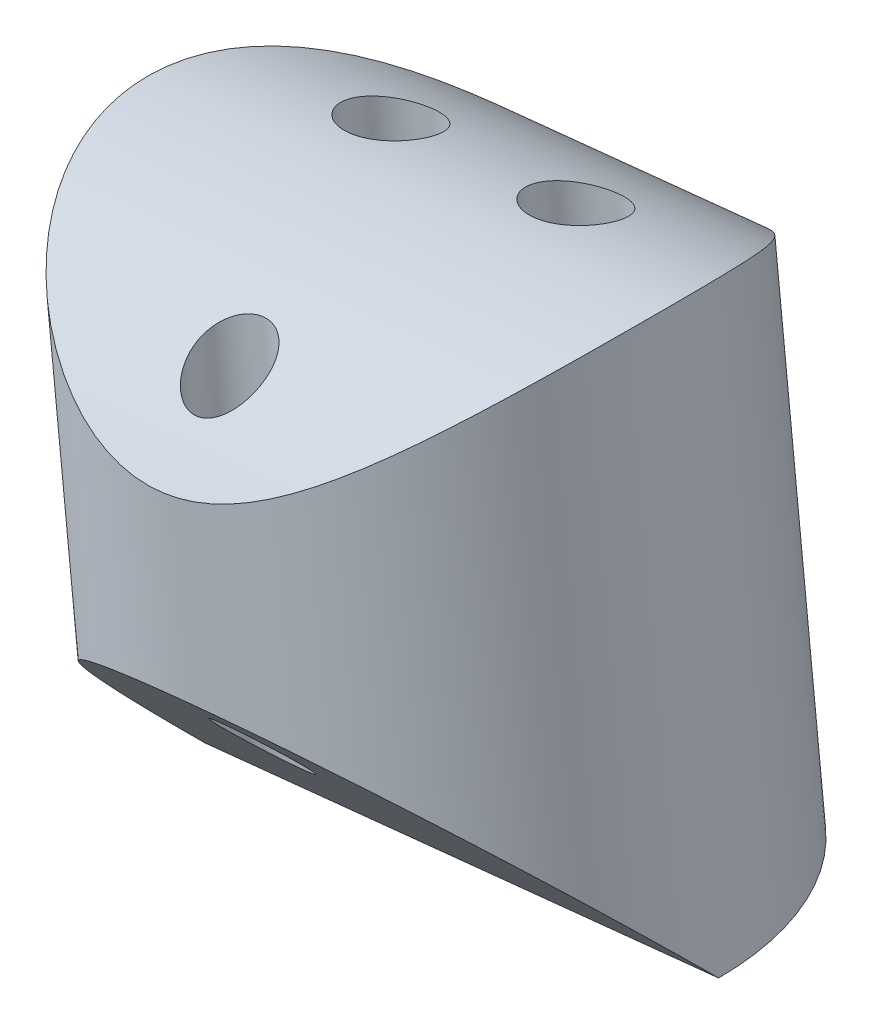
SolidWorks part; units mm, degrees
ref_plane "Front Plane" through (0, 0, 0) normal (0, 0, 1) x (1, 0, 0)
ref_plane "Top Plane" through (0, 0, 0) normal (0, 1, 0) x (1, 0, 0)
ref_plane "Right Plane" through (0, 0, 0) normal (1, 0, 0) x (0, 0, -1)
sketch "Sketch2" plane through (0, 0, 0) normal (0, 0, 1) x (1, 0, 0)
  line L0 (0, 0) -> (90, 0)
  line L1 (90, 0) -> (90, 120)
  line L2 (90, 120) -> (0, 120)
  line L3 (0, 120) -> (0, 0)
  line L4 (0, 120) -> (-10, 120)
  line L5 (-10, 120) -> (-10, 16.9491)
  line L6 (-10, 120) -> (57.5, 127)
  line L7 (57.5, 127) -> (90, 124)
  line L8 (90, 120) -> (99, 60)
  line L10 (90, 124) -> (90, 120)
  line L11 (5.9147, 0) -> (5.9147, -25)
  line L12 (5.9147, -25) -> (-4.0853, -25)
  line L13 (-4.0853, -29) -> (-4.0853, 0)
  line L14 (80, 0) -> (80, -25)
  line L15 (80, -25) -> (90, -25)
  line L16 (90, -29) -> (90, 0)
  line L17 (15.7927, 122.6748) -> (5.4776, 222.1414)
  line L18 (5.4776, 222.1414) -> (21.3923, 223.7918)
  line L19 (21.3923, 223.7918) -> (31.7073, 124.3252)
  line L20 (7.6492, 201.201) -> (23.5639, 202.8514)
  line L21 (10.9066, 169.7905) -> (26.8212, 171.441)
  line L22 (-10, 120) -> (-20.0396, 216.8108)
  line L23 (-20.0396, 216.8108) -> (-4.125, 218.4612)
  line L24 (-4.125, 218.4612) -> (5.9147, 121.6504)
  line L25 (-17.926, 196.4296) -> (-2.0114, 198.08)
  line L26 (-14.7556, 165.8578) -> (1.159, 167.5082)
  line L27 (57.5, 127) -> (46.9095, 229.1223)
  line L28 (46.9095, 229.1223) -> (30.9949, 227.4719)
  line L29 (30.9949, 227.4719) -> (41.5853, 125.3496)
  line L30 (33.2245, 205.9725) -> (49.1391, 207.6229)
  line L31 (36.5688, 173.7233) -> (52.4835, 175.3737)
  line L34 (90, 124) -> (99.1917, 223.5767)
  line L35 (99.1917, 223.5767) -> (83.2594, 225.0473)
  line L36 (83.2594, 225.0473) -> (74.0677, 125.4707)
  line L38 (81.3243, 204.0838) -> (97.2566, 202.6132)
  line L39 (78.4217, 172.6386) -> (94.354, 171.1679)
  line L40 (62.4078, 79.6749) -> (57.5, 127) construction
  line L41 (41.5853, 125.3496) -> (46.4931, 78.0244) construction
  line L42 (46.4931, 78.0244) -> (62.4078, 79.6749) construction
  line L43 (31.7073, 124.3252) -> (36.6151, 77.0001) construction
  line L44 (36.6151, 77.0001) -> (20.7005, 75.3496) construction
  line L45 (20.7005, 75.3496) -> (15.7927, 122.6748) construction
  line L46 (5.9147, 121.6504) -> (10.8224, 74.3253) construction
  line L47 (10.8224, 74.3253) -> (-5.0922, 72.6749) construction
  line L48 (-5.0922, 72.6749) -> (-10, 120) construction
  line L49 (74.0677, 125.4707) -> (69.6944, 78.0931) construction
  line L50 (69.6944, 78.0931) -> (85.7624, 78.0931) construction
  line L51 (85.7624, 78.0931) -> (90, 124) construction
  line L52 (-12.0823, 217.636) -> (10.4873, 0) construction
  line L53 (13.4349, 222.9666) -> (36.5574, 0) construction
  line L54 (38.9522, 228.2971) -> (62.6275, 0) construction
  line L55 (91.2256, 224.312) -> (70.5198, 0) construction
  line L59 (99, 60) -> (93.5277, 44.9649)
  line L60 (99, 60) -> (169.4769, 34.3485)
  line L61 (169.4769, 34.3485) -> (164.0046, 19.3134)
  line L62 (164.0046, 19.3134) -> (93.5277, 44.9649)
  line L63 (90, -2) -> (100, -2)
  line L64 (141.2862, 44.6091) -> (135.8138, 29.574)
  line L65 (99, 60) -> (55.7741, 75.7329) construction
  line L66 (55.7741, 75.7329) -> (50.3018, 60.6978) construction
  line L67 (100, -2) -> (100, -29)
  line L70 (-4.0853, -2) -> (-14.0853, -2)
  line L71 (-14.0853, -2) -> (-14.0853, -29)
  line L74 (-4.0853, 0) -> (0, 0)
  line L75 (-14.0853, -29) -> (-14.0853, -112.587)
  line L76 (-14.0853, -112.587) -> (100, -112.587)
  line L77 (100, -112.587) -> (100, -29)
  line L78 (-14.0853, -29) -> (100, -29)
  line L79 (-14.0853, -14.5) -> (100, -14.5) construction
  line L80 (31.7073, -112.587) -> (31.7073, -122.6232)
  line L81 (31.7073, -122.6232) -> (42.9573, -122.6232)
  line L82 (42.9573, -122.6232) -> (42.9573, -112.587)
  line L83 (-14.0853, -112.587) -> (-88.3667, -112.587)
  line L84 (-88.3667, -112.587) -> (-88.3667, -128.2699)
  line L85 (-88.3667, -128.2699) -> (169.4958, -128.2699)
  line L86 (169.4958, -128.2699) -> (169.4958, -112.587)
  line L87 (169.4958, -112.587) -> (100, -112.587)
  line L88 (90, 60) -> (-10, 60) construction
  line L89 (50.3018, 60.6978) -> (93.5277, 44.9649) construction
  line L90 (87.2806, 55.7521) -> (166.7408, 26.8309) construction
  line L91 (87.2806, 55.7521) -> (82.1749, 52.5336) construction
  line L92 (82.1749, 52.5336) -> (77.3257, 0) construction
  line L93 (83.1185, 56.6957) -> (86.337, 51.59) construction
  arc A0 (-10, 16.9491) -> (-4.0853, 0) centre (14.9876, 16.1624) ccw
  arc A1 (93.5277, 44.9649) -> (90, 0) centre (-126.4069, 39.5988) cw
  point P42 (41.1818, 206.7977)
  point P100 (84.7278, 54.1428)
  point P101 (84.7278, 54.1428)
  dimension "D11" = 47.3684
  dimension "D35" = 9
  dimension "D32" = 220
  dimension "D36" = 25
  dimension "D1" = 120
  dimension "D2" = 90
  dimension "D3" = 10
  dimension "D5" = 67.862
  dimension "D6" = 7
  dimension "D7" = 4
  dimension "D8" = 16
  dimension "D9" = 16
  dimension "D10" = 100
  dimension "D12" = 31.5789
  dimension "D13" = 16
  dimension "D14" = 16
  dimension "D15" = 16
  dimension "D16" = 25.7927
  dimension "D17" = 100
  dimension "D18" = 21.0526
  dimension "D19" = 31.5789
  dimension "D20" = 97.33
  dimension "D21" = 102.67
  dimension "D22" = 20.4905
  dimension "D23" = 30.7358
  dimension "D24" = 21.6147
  dimension "D25" = 32.4221
  dimension "D26" = 25
  dimension "D28" = 25
  dimension "D29" = 75
  dimension "D30" = 47.5789
  dimension "D31" = 30
  dimension "D33" = 46
  dimension "D34" = 20
  dimension "D37" = 2
  dimension "D38" = 2
  dimension "D39" = 27
  dimension "D40" = 10
  dimension "D41" = 10
  dimension "D42" = 27
  dimension "D43" = 14.5
  dimension "D44" = 127.5
ref_plane "Plane1" through (87.2806, 55.7521, 0) normal (-0.846, -0.5333, 0) x (0, 0, 1)
ref_plane "Plane2" through (82.1749, 52.5336, 0) normal (-0.0919, -0.9958, 0) x (-0.9958, 0.0919, 0)
ref_plane "Plane3" through (91.2256, 224.312, 0) normal (-0.0919, -0.9958, 0) x (-0.9958, 0.0919, 0)
ref_plane "Plane4" through (38.9522, 228.2971, 0) normal (0.1032, -0.9947, 0) x (-0.9947, -0.1032, 0)
ref_plane "Plane5" through (13.4349, 222.9666, 0) normal (0.1032, -0.9947, 0) x (-0.9947, -0.1032, 0)
ref_plane "Plane7" through (166.7408, 26.8309, 0) normal (0.9397, -0.342, 0) x (0, 0, -1)
ref_plane "Plane8" through (110.4217, -40.1902, 0) normal (0.9397, -0.342, 0) x (0, 0, -1)
ref_plane "Plane9" through (19.3664, 209.803, 0) normal (-0.0919, -0.9958, 0) x (-0.9958, 0.0919, 0)
ref_plane "Plane10" through (16.4638, 178.3578, 0) normal (-0.0919, -0.9958, 0) x (-0.9958, 0.0919, 0)
ref_plane "Plane11" through (-20.7793, 200.3721, 0) normal (0.1032, -0.9947, 0) x (-0.9947, -0.1032, 0)
ref_plane "Plane12" through (-17.435, 168.1229, 0) normal (0.1032, -0.9947, 0) x (-0.9947, -0.1032, 0)
ref_plane "Plane13" through (-20.5619, 198.2754, 0) normal (0.1032, -0.9947, 0) x (-0.9947, -0.1032, 0)
ref_plane "Plane14" through (-17.3045, 166.8649, 0) normal (0.1032, -0.9947, 0) x (-0.9947, -0.1032, 0)
ref_plane "Plane15" through (-12.0823, 217.636, 0) normal (0.1032, -0.9947, 0) x (-0.9947, -0.1032, 0)
ref_plane "Plane16" through (-20.3445, 196.1788, 0) normal (0.1032, -0.9947, 0) x (-0.9947, -0.1032, 0)
ref_plane "Plane17" through (-17.1741, 165.607, 0) normal (0.1032, -0.9947, 0) x (-0.9947, -0.1032, 0)
ref_plane "Plane18" through (12.1098, 131.1899, 0) normal (-0.0919, -0.9958, 0) x (-0.9958, 0.0919, 0)
ref_plane "Plane19" through (-12.4184, 119.7492, 0) normal (0.1032, -0.9947, 0) x (-0.9947, -0.1032, 0)
ref_plane "Plane20" through (0, 0, 0) normal (0, 0, 1) x (0.1032, -0.9947, 0)
ref_plane "Plane21" through (0, 0, 0) normal (0, 0, 1) x (-0.0919, -0.9958, 0)
ref_plane "Plane22" through (10.3758, 1.076, 0) normal (-0.9947, -0.1032, 0) x (0.1032, -0.9947, 0)
ref_plane "Plane23" through (36.1684, 3.7508, 0) normal (-0.9947, -0.1032, 0) x (0.1032, -0.9947, 0)
ref_plane "Plane24" through (61.9611, 6.4256, 0) normal (-0.9947, -0.1032, 0) x (0.1032, -0.9947, 0)
ref_plane "Plane25" through (69.924, -6.4545, 0) normal (-0.9958, 0.0919, 0) x (-0.0919, -0.9958, 0)
sketch "Sketch3" plane through (-12.0823, 217.636, 0) normal (0.1032, -0.9947, 0) x (-0.9947, -0.1032, 0)
  circle A0 centre (0, 0) radius 10
  dimension "D1" = 20
extrude "Boss-Extrude1" add sketch "Sketch3" along normal blind 21.6147
sketch "Sketch4" plane through (10.3758, 1.076, 0) normal (-0.9947, -0.1032, 0) x (0.1032, -0.9947, 0)
  line L0 (-217.7214, 10) -> (-212.7214, 10)
  line L1 (-196.1067, 10) -> (-217.7214, 10) construction
  line L2 (-217.7214, 10) -> (-217.7214, -10)
  line L3 (-217.7214, -10) -> (-212.7214, -10)
  line L4 (-217.7214, -10) -> (-196.1067, -10) construction
  arc A1 (-212.7214, 10) -> (-212.7214, -10) centre (-204.6027, 0) ccw
  dimension "D1" = 5
extrude "Cut-Extrude1" cut sketch "Sketch4" against normal through all and the other way through all
sketch "Sketch5" plane through (10.3758, 1.076, 0) normal (-0.9947, -0.1032, 0) x (0.1032, -0.9947, 0)
  line L0 (-196.1067, 0) -> (-206.1067, 10)
  line L1 (-196.1067, -10) -> (-196.1067, 10) construction
  line L2 (-196.1067, 10) -> (-212.7214, 10) construction
  line L3 (-206.1067, 10) -> (-196.1067, 10)
  line L4 (-196.1067, 10) -> (-196.1067, 0)
  dimension "D1" = 45
extrude "Cut-Extrude2" cut sketch "Sketch5" against normal through all and the other way through all
sketch "Sketch7" plane through (10.3758, 1.076, 0) normal (-0.9947, -0.1032, 0) x (0.1032, -0.9947, 0)
  line L2 (-191.1067, 0) -> (-196.1067, -5)
  line L5 (-201.1067, 5) -> (-196.1067, 0)
  line L6 (-196.1067, 0) -> (-206.1067, 10) construction
  line L8 (-213.7055, 0) -> (7.2742, 0) construction
  line L9 (-191.1067, 0) -> (-191.1067, 5)
  line L10 (-191.1067, 5) -> (-201.1067, 5)
  line L11 (-196.1067, 0) -> (-191.1067, 5) construction
  line L12 (-196.1067, -10) -> (-196.1067, 0) construction
  line L13 (-196.1067, -5) -> (-196.1067, 0)
  line L14 (-194.6065, 0) -> (-191.5003, 0) construction
  dimension "D1" = 45
sketch "Sketch8" plane through (-12.0823, 217.636, 0) normal (0.1032, -0.9947, 0) x (-0.9947, -0.1032, 0)
  line L0 (8, 0) -> (-8, 0) construction
  circle A0 centre (-3.6, 3) radius 1.6
  circle A1 centre (3.6, 3) radius 1.6
  circle A3 centre (0, -7) radius 1.4
  point P6 (0, 0)
  dimension "D1" = 3.2
  dimension "D2" = 3.2
  dimension "D7" = 2.8
  dimension "D3" = 3
  dimension "D4" = 3
  dimension "D5" = 3.6
  dimension "D6" = 3.6
  dimension "D8" = 7
extrude "Cut-Extrude3" cut sketch "Sketch8" against normal through all and the other way through all
sketch "Sketch9" plane through (-20.2285, 195.0606, 0) normal (0.1032, -0.9947, 0) x (0.9947, 0.1032, 0)
  line L0 (2.4314, -6) -> (18.4314, -6)
  arc A0 (0.4314, 0) -> (20.4314, 0) centre (10.4314, 0) ccw construction
  arc A1 (2.4314, -6) -> (18.4314, -6) centre (10.4314, 0) ccw
  dimension "D1" = 6
